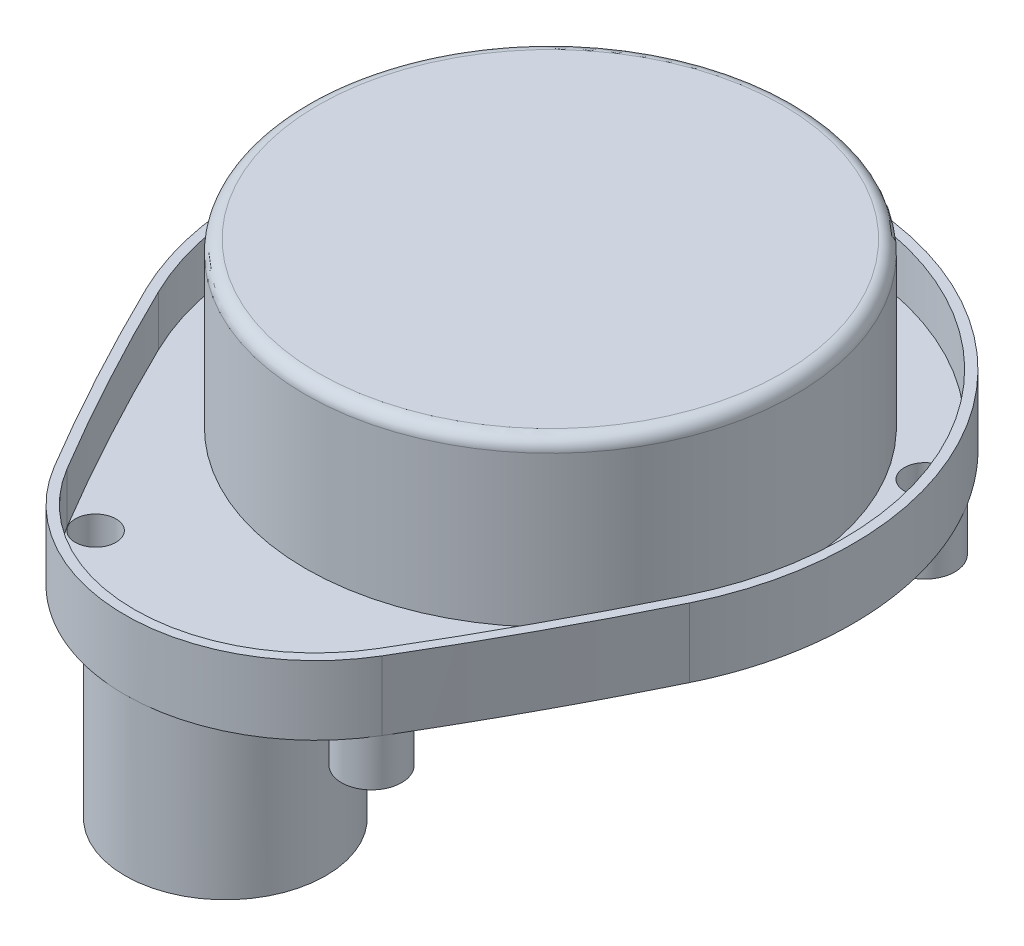
SolidWorks part; units mm, degrees
material "ABS"
ref_plane "Front Plane" through (0, 0, 0) normal (0, 0, 1) x (1, 0, 0)
ref_plane "Top Plane" through (0, 0, 0) normal (0, 1, 0) x (1, 0, 0)
ref_plane "Right Plane" through (0, 0, 0) normal (1, 0, 0) x (0, 0, -1)
sketch "Sketch1" plane through (0, 0, 0) normal (0, 1, 0) x (1, 0, 0)
  line L0 (0, 48.2) -> (0, -67.8) construction
  line L1 (0, -67.8) -> (21.7641, -67.8) construction
  line L3 (37, 22.6839) -> (0, 22.6839) construction
  line L4 (22, -50.494) -> (0, -50.494) construction
  circle A0 centre (0, 0) radius 48.2 construction
  circle A1 centre (37, 22.6839) radius 4.8
  circle A2 centre (22, -50.494) radius 4.8
  circle A3 centre (-37, 22.6839) radius 4.8
  circle A4 centre (-22, -50.494) radius 4.8
  arc A5 (26.1244, -52.9494) -> (-26.1244, -52.9494) centre (0, -37.3963) cw
  arc A6 (-26.1244, -52.9494) -> (-43.317, -21.1395) centre (348.4365, 170.0439) cw
  arc A7 (-43.317, -21.1395) -> (0, 48.2) centre (0, 0) cw
  arc A8 (43.317, -21.1395) -> (0, 48.2) centre (0, 0) ccw
  arc A9 (26.1244, -52.9494) -> (43.317, -21.1395) centre (-348.4365, 170.0439) ccw
  dimension "D1" = 96.4
  dimension "D2" = 9.6
  dimension "D4" = 37
  dimension "D3" = 116
  dimension "D5" = 22
  dimension "D6" = 94
extrude "Boss-Extrude2" add sketch "Sketch1" along normal blind 3 contours A7 A8 A9 A5 A6
sketch "Sketch3" plane through (0, 0, 0) normal (0, -1, 0) x (1, 0, 0)
  circle A1 centre (-37, -22.6839) radius 4.8
  circle A2 centre (-37, -22.6839) radius 4.8
  circle A3 centre (22, 50.494) radius 4.8
  arc A4 (-26.1244, 52.9494) -> (-43.317, 21.1395) centre (348.4365, -170.0439) ccw
  arc A5 (-43.317, 21.1395) -> (43.317, 21.1395) centre (0, 0) ccw
  arc A6 (43.317, 21.1395) -> (26.1244, 52.9494) centre (-348.4365, -170.0439) ccw
  arc A7 (26.1244, 52.9494) -> (-26.1244, 52.9494) centre (0, 37.3963) ccw
  arc A8 (-26.1244, 52.9494) -> (-43.317, 21.1395) centre (348.4365, -170.0439) ccw
  arc A9 (-43.317, 21.1395) -> (43.317, 21.1395) centre (0, 0) ccw
  arc A10 (43.317, 21.1395) -> (26.1244, 52.9494) centre (-348.4365, -170.0439) ccw
  arc A11 (26.1244, 52.9494) -> (-26.1244, 52.9494) centre (0, 37.3963) ccw
  circle A12 centre (22, 50.494) radius 4.8
  circle A13 centre (37, -22.6839) radius 4.8
  circle A14 centre (37, -22.6839) radius 4.8
  circle A15 centre (-22, 50.494) radius 4.8
  circle A16 centre (-22, 50.494) radius 4.8
  arc A19 (26.1244, 52.9494) -> (-26.1244, 52.9494) centre (0, 37.3963) ccw
  arc A20 (-26.1244, 52.9494) -> (-43.317, 21.1395) centre (348.4365, -170.0439) ccw
  arc A21 (-43.317, 21.1395) -> (0, -48.2) centre (0, 0) ccw
  arc A22 (0, -48.2) -> (43.317, 21.1395) centre (0, 0) ccw
  arc A23 (43.317, 21.1395) -> (26.1244, 52.9494) centre (-348.4365, -170.0439) ccw
  arc A24 (26.1244, 52.9494) -> (-26.1244, 52.9494) centre (0, 37.3963) ccw
  arc A25 (-26.1244, 52.9494) -> (-43.317, 21.1395) centre (348.4365, -170.0439) ccw
  arc A26 (-43.317, 21.1395) -> (0, -48.2) centre (0, 0) ccw
  arc A27 (0, -48.2) -> (43.317, 21.1395) centre (0, 0) ccw
  arc A28 (43.317, 21.1395) -> (26.1244, 52.9494) centre (-348.4365, -170.0439) ccw
  dimension "D1" = 0
  dimension "D2" = 0
  dimension "D3" = 0
  dimension "D4" = 0
  dimension "D5" = 0
  dimension "D6" = 0
extrude "Boss-Extrude3" add sketch "Sketch3" along normal blind 7.4 contours A14 | A2 | A16 | A12 region at (-37, 0, -22.6839) region at (37, 0, -22.6839) region at (22, 0, 50.494) region at (-22, 0, 50.494)
sketch "Sketch6" plane through (0, 0, 0) normal (0, -1, 0) x (1, 0, 0)
  line L0 (0, 67.8) -> (0, 51.8) construction
  arc A0 (26.1244, 52.9494) -> (-26.1244, 52.9494) centre (0, 37.3963) ccw construction
  circle A1 centre (0, 51.8) radius 16
  dimension "D1" = 32
extrude "Boss-Extrude6" add sketch "Sketch6" along normal blind 25
sketch "Sketch4" plane through (0, 0, 0) normal (0, -1, 0) x (1, 0, 0)
  circle A0 centre (0, 0) radius 38.5
  dimension "D1" = 77
extrude "Boss-Extrude4" add sketch "Sketch4" along normal blind 6
sketch "Sketch5" plane through (0, -6, 0) normal (0, -1, 0) x (1, 0, 0)
  circle A0 centre (0, 0) radius 28.2
  dimension "D1" = 56.4
extrude "Boss-Extrude5" add sketch "Sketch5" along normal blind 1.4
chamfer "Chamfer1" distance 1.4 angle 45 1 edges at (0, -7.4, -28.2)
fillet "Fillet2" radius 2 1 edges at (0, -6, -38.5)
sketch "Sketch7" plane through (0, -7.4, 0) normal (0, -1, 0) x (1, 0, 0)
  circle A0 centre (37, -22.6839) radius 3.25
  circle A1 centre (-37, -22.6839) radius 3.25
  circle A2 centre (-22, 50.494) radius 3.25
  circle A3 centre (22, 50.494) radius 3.25
  dimension "D1" = 6.5
extrude "Cut-Extrude1" cut sketch "Sketch7" against normal blind 2
chamfer "Chamfer2" distance 0.5 angle 45 4 edges at (37, -7.4, -25.9339) (-37, -7.4, -25.9339) (-22, -7.4, 47.244) (22, -7.4, 47.244)
sketch "Sketch9" plane through (0, -5.4, 0) normal (0, -1, 0) x (1, 0, 0)
  circle A0 centre (22, 50.494) radius 1.5
  circle A1 centre (-22, 50.494) radius 1.5
  circle A2 centre (-37, -22.6839) radius 1.5
  circle A3 centre (37, -22.6839) radius 1.5
  dimension "D1" = 3
extrude "Cut-Extrude2" cut sketch "Sketch9" against normal through all
sketch "Sketch10" plane through (0, 3, 0) normal (0, 1, 0) x (1, 0, 0)
  arc A0 (24.8355, -52.1821) -> (41.9689, -20.4817) centre (-348.4365, 170.0439) ccw
  arc A1 (41.9689, -20.4817) -> (-41.9689, -20.4817) centre (0, 0) ccw
  arc A2 (-41.9689, -20.4817) -> (-24.8355, -52.1821) centre (348.4365, 170.0439) ccw
  arc A3 (-24.8355, -52.1821) -> (24.8355, -52.1821) centre (0, -37.3963) ccw
  arc A4 (-43.317, -21.1395) -> (-26.1244, -52.9494) centre (348.4365, 170.0439) ccw
  arc A5 (-26.1244, -52.9494) -> (26.1244, -52.9494) centre (0, -37.3963) ccw
  arc A6 (26.1244, -52.9494) -> (43.317, -21.1395) centre (-348.4365, 170.0439) ccw
  arc A7 (43.317, -21.1395) -> (-43.317, -21.1395) centre (0, 0) ccw
  arc A8 (-43.317, -21.1395) -> (-26.1244, -52.9494) centre (348.4365, 170.0439) ccw
  arc A9 (-26.1244, -52.9494) -> (26.1244, -52.9494) centre (0, -37.3963) ccw
  arc A10 (26.1244, -52.9494) -> (43.317, -21.1395) centre (-348.4365, 170.0439) ccw
  arc A11 (43.317, -21.1395) -> (-43.317, -21.1395) centre (0, 0) ccw
  arc A12 (26.1244, -52.9494) -> (43.317, -21.1395) centre (-348.4365, 170.0439) ccw construction
  arc A19 (-26.1244, -52.9494) -> (26.1244, -52.9494) centre (0, -37.3963) ccw
  arc A20 (-43.317, -21.1395) -> (-26.1244, -52.9494) centre (348.4365, 170.0439) ccw
  arc A21 (0, 48.2) -> (-43.317, -21.1395) centre (0, 0) ccw
  arc A22 (43.317, -21.1395) -> (0, 48.2) centre (0, 0) ccw
  arc A23 (26.1244, -52.9494) -> (43.317, -21.1395) centre (-348.4365, 170.0439) ccw
  arc A24 (-26.1244, -52.9494) -> (26.1244, -52.9494) centre (0, -37.3963) ccw
  arc A25 (-43.317, -21.1395) -> (-26.1244, -52.9494) centre (348.4365, 170.0439) ccw
  arc A26 (0, 48.2) -> (-43.317, -21.1395) centre (0, 0) ccw
  arc A27 (43.317, -21.1395) -> (0, 48.2) centre (0, 0) ccw
  arc A28 (26.1244, -52.9494) -> (43.317, -21.1395) centre (-348.4365, 170.0439) ccw
  arc M18 (-43.317, -21.1395) -> (-26.1244, -52.9494) centre (348.4365, 170.0439) ccw
  arc M19 (-26.1244, -52.9494) -> (26.1244, -52.9494) centre (0, -37.3963) ccw
  arc M20 (26.1244, -52.9494) -> (43.317, -21.1395) centre (-348.4365, 170.0439) ccw
  arc M21 (43.317, -21.1395) -> (-43.317, -21.1395) centre (0, 0) ccw
  dimension "D1" = 0
  dimension "D2" = 1.5
  dimension "D5" = 0
extrude "Boss-Extrude7" add sketch "Sketch10" along normal blind 8 contours A11 A3 A2 A1 A0 M21 M18 M19 M20 region at (-40.751, 3, -25.4575)
sketch "Sketch14" plane through (0, 3, 0) normal (0, 1, 0) x (1, 0, 0)
  circle A0 centre (-37, 22.6839) radius 3.25
  circle A1 centre (37, 22.6839) radius 3.25
  circle A2 centre (22, -50.494) radius 3.25
  circle A3 centre (-22, -50.494) radius 3.25
  dimension "D1" = 6.5
extrude "Cut-Extrude3" cut sketch "Sketch14" against normal blind 6
sketch "Sketch15" plane through (0, 3, 0) normal (0, 1, 0) x (1, 0, 0)
  circle A0 centre (0, 0) radius 39
  dimension "D1" = 78
extrude "Boss-Extrude8" add sketch "Sketch15" along normal blind 26
fillet "Fillet3" radius 2 1 edges at (0, 29, 39)
